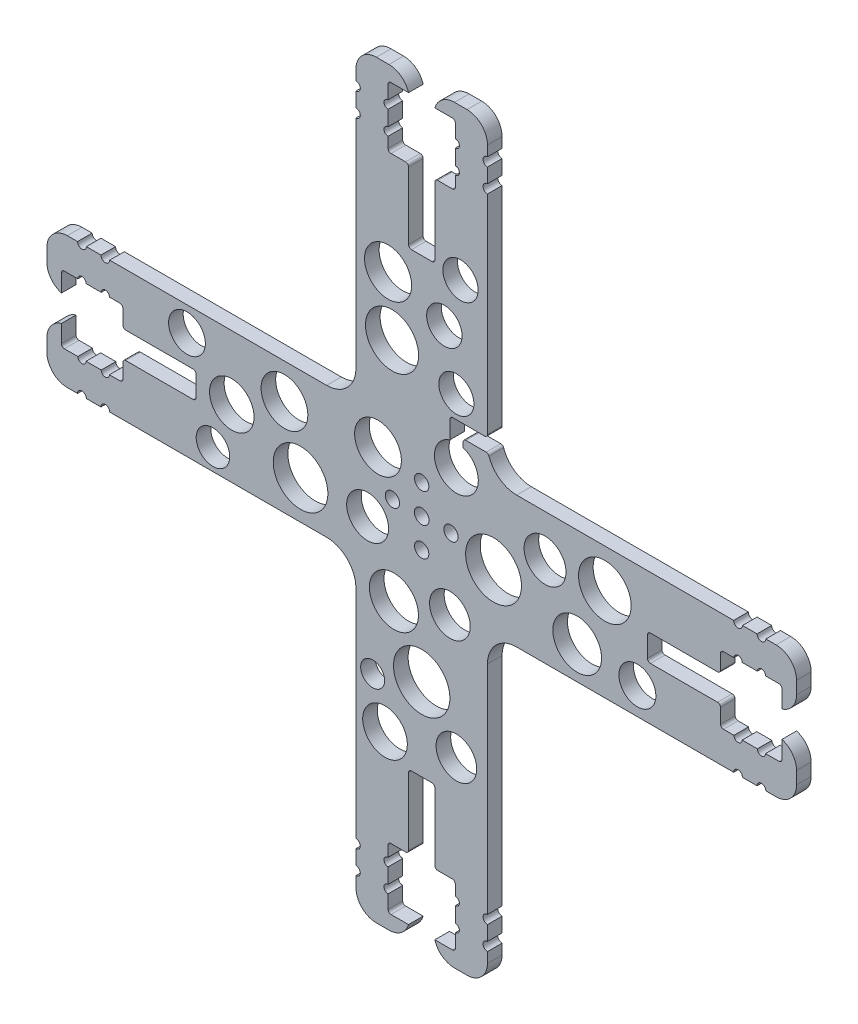
SolidWorks part; units mm, degrees
ref_plane "Front Plane" through (0, 0, 0) normal (0, 0, 1) x (1, 0, 0)
ref_plane "Top Plane" through (0, 0, 0) normal (0, 1, 0) x (1, 0, 0)
ref_plane "Right Plane" through (0, 0, 0) normal (1, 0, 0) x (0, 0, -1)
sketch "Esquisse1" plane through (0, 0, 0) normal (0, 0, 1) x (1, 0, 0)
  line L0 (0, 159.2308) -> (0, -15.7846) construction
  line L1 (-22.5, 22.5) -> (-22.5, 128.2082)
  line L2 (-22.5, 128.2082) -> (-4.5, 128.2082)
  line L3 (-4.5, 128.2082) -> (-4.5, 123.2082)
  line L4 (-4.5, 123.2082) -> (-11.5, 123.2082)
  line L5 (-11.5, 123.2082) -> (-11.5, 102.2082)
  line L6 (-11.5, 102.2082) -> (-4.5, 102.2082)
  line L7 (-4.5, 102.2082) -> (-4.5, 77.2082)
  line L8 (-4.5, 77.2082) -> (4.5, 77.2082)
  line L9 (4.5, 77.2082) -> (4.5, 102.2082)
  line L10 (4.5, 102.2082) -> (11.5, 102.2082)
  line L11 (11.5, 102.2082) -> (11.5, 123.2082)
  line L12 (11.5, 123.2082) -> (4.5, 123.2082)
  line L13 (4.5, 123.2082) -> (4.5, 128.2082)
  line L14 (4.5, 128.2082) -> (22.5, 128.2082)
  line L15 (22.5, 128.2082) -> (22.5, 22.5)
  line L16 (22.5, 22.5) -> (128.2082, 22.5)
  line L17 (128.2082, 22.5) -> (128.2082, 4.5)
  line L18 (128.2082, 4.5) -> (123.2082, 4.5)
  line L19 (123.2082, 4.5) -> (123.2082, 11.5)
  line L20 (123.2082, 11.5) -> (102.2082, 11.5)
  line L21 (102.2082, 11.5) -> (102.2082, 4.5)
  line L22 (102.2082, 4.5) -> (77.2082, 4.5)
  line L23 (77.2082, 4.5) -> (77.2082, -4.5)
  line L24 (77.2082, -4.5) -> (102.2082, -4.5)
  line L25 (102.2082, -4.5) -> (102.2082, -11.5)
  line L26 (102.2082, -11.5) -> (123.2082, -11.5)
  line L27 (123.2082, -11.5) -> (123.2082, -4.5)
  line L28 (123.2082, -4.5) -> (128.2082, -4.5)
  line L29 (128.2082, -4.5) -> (128.2082, -22.5)
  line L30 (128.2082, -22.5) -> (22.5, -22.5)
  line L31 (22.5, -22.5) -> (22.5, -128.2082)
  line L32 (22.5, -128.2082) -> (4.5, -128.2082)
  line L33 (4.5, -128.2082) -> (4.5, -123.2082)
  line L34 (4.5, -123.2082) -> (11.5, -123.2082)
  line L35 (11.5, -123.2082) -> (11.5, -102.2082)
  line L36 (11.5, -102.2082) -> (4.5, -102.2082)
  line L37 (4.5, -102.2082) -> (4.5, -77.2082)
  line L38 (4.5, -77.2082) -> (-4.5, -77.2082)
  line L39 (-4.5, -77.2082) -> (-4.5, -102.2082)
  line L40 (-4.5, -102.2082) -> (-11.5, -102.2082)
  line L41 (-11.5, -102.2082) -> (-11.5, -123.2082)
  line L42 (-11.5, -123.2082) -> (-4.5, -123.2082)
  line L43 (-4.5, -123.2082) -> (-4.5, -128.2082)
  line L44 (-4.5, -128.2082) -> (-22.5, -128.2082)
  line L45 (-22.5, -128.2082) -> (-22.5, -22.5)
  line L46 (-22.5, -22.5) -> (-128.2082, -22.5)
  line L47 (-128.2082, -22.5) -> (-128.2082, -4.5)
  line L48 (-128.2082, -4.5) -> (-123.2082, -4.5)
  line L49 (-123.2082, -4.5) -> (-123.2082, -11.5)
  line L50 (-123.2082, -11.5) -> (-102.2082, -11.5)
  line L51 (-102.2082, -11.5) -> (-102.2082, -4.5)
  line L52 (-102.2082, -4.5) -> (-77.2082, -4.5)
  line L53 (-77.2082, -4.5) -> (-77.2082, 4.5)
  line L54 (-77.2082, 4.5) -> (-102.2082, 4.5)
  line L55 (-102.2082, 4.5) -> (-102.2082, 11.5)
  line L56 (-102.2082, 11.5) -> (-123.2082, 11.5)
  line L57 (-123.2082, 11.5) -> (-123.2082, 4.5)
  line L58 (-123.2082, 4.5) -> (-128.2082, 4.5)
  line L59 (-128.2082, 4.5) -> (-128.2082, 22.5)
  line L60 (-128.2082, 22.5) -> (-22.5, 22.5)
  line L61 (-24.5698, 123.2082) -> (43.5937, 123.2082) construction
  line L62 (123.2082, 24.5698) -> (123.2082, -43.5937) construction
  line L63 (24.5698, -123.2082) -> (-43.5937, -123.2082) construction
  line L64 (-123.2082, -24.5698) -> (-123.2082, 43.5937) construction
  line L65 (-148.0023, 0) -> (163.5643, 0) construction
  circle A0 centre (0, 0) radius 2.5
  circle A1 centre (-80.2824, 14.1103) radius 6.2904
  circle A2 centre (-64.9494, 0.6296) radius 7.6187
  circle A3 centre (-41.4305, -9.3429) radius 9.3429
  circle A4 centre (-46.9444, 10.5137) radius 8
  circle A5 centre (-71.3951, -15.2254) radius 5.734
  circle A6 centre (42.1879, 8.0594) radius 7.1686
  circle A7 centre (24.5698, -3.6089) radius 9.551
  circle A8 centre (11.8627, 20.2507) radius 7.5
  circle A9 centre (-14.9441, 12.9829) radius 8
  circle A10 centre (-10.1433, 47.064) radius 9.0827
  circle A11 centre (11.8627, 42.1489) radius 6
  circle A12 centre (-18.5, -9.3429) radius 7.1678
  circle A13 centre (0, -49.0636) radius 9.6471
  circle A14 centre (-16.7647, -55.0598) radius 4.1145
  circle A15 centre (11.8627, -65.5127) radius 6.9485
  circle A16 centre (-12.5425, -70.0598) radius 7.6364
  circle A17 centre (9.6471, -24.3763) radius 6.9631
  circle A18 centre (-9.5049, -29.9285) radius 8.3862
  circle A19 centre (53.1834, -11.3064) radius 8.3279
  circle A20 centre (62.6447, 9.2453) radius 9
  circle A21 centre (13.2718, 76.5762) radius 6.033
  circle A22 centre (-11.5, 66.6049) radius 8.0615
  circle A23 centre (7.7598, 60.3029) radius 6.0616
  circle A24 centre (73.7695, -13.2445) radius 6.3276
  circle A25 centre (10, 0) radius 2.4404
  circle A26 centre (0, -10) radius 2.4404
  circle A27 centre (-10, 0) radius 2.4404
  circle A28 centre (0, 10) radius 2.4404
  point P19 (0, 77.2082)
  point P23 (0, 123.2082)
  point P74 (0, 0)
  point P76 (123.2082, 0)
  point P81 (0, -123.2082)
  point P84 (-123.2082, 0)
  point P129 (0, 120.2082)
  point P132 (120.2082, 0)
  point P133 (0, -120.2082)
  point P136 (-120.2082, 0)
  point P144 (0, 0)
  dimension "D6" = 4
  dimension "D9" = 170
  dimension "D10" = 10
  dimension "D1" = 9
  dimension "D2" = 23
  dimension "D3" = 21
  dimension "D4" = 45
  dimension "D5" = 25
  dimension "D7" = 3
  dimension "D8" = 5
  dimension "D11" = 4
extrude "Boss.-Extru.1" add sketch "Esquisse1" along normal blind 5
fillet "Congé1" radius 7 16 edges at (128.2082, 4.5, 2.5) (128.2082, -4.5, 2.5) (4.5, -128.2082, 2.5) (-4.5, -128.2082, 2.5) (-128.2082, -4.5, 2.5) (-128.2082, 4.5, 2.5) (-4.5, 128.2082, 2.5) (4.5, 128.2082, 2.5) (22.5, 128.2082, 2.5) (-22.5, 128.2082, 2.5) (-128.2082, 22.5, 2.5) (-128.2082, -22.5, 2.5) (-22.5, -128.2082, 2.5) (22.5, -128.2082, 2.5) (128.2082, -22.5, 2.5) (128.2082, 22.5, 2.5)
fillet "Congé2" radius 10 4 edges at (-22.5, 22.5, 2.5) (22.5, 22.5, 2.5) (22.5, -22.5, 2.5) (-22.5, -22.5, 2.5)
fillet "Congé3" radius 1 32 edges at (123.2082, -11.5, 2.5) (102.2082, -11.5, 2.5) (77.2082, -4.5, 2.5) (123.2082, 11.5, 2.5) (102.2082, -4.5, 2.5) (102.2082, 11.5, 2.5) (77.2082, 4.5, 2.5) (102.2082, 4.5, 2.5) (11.5, 123.2082, 2.5) (11.5, 102.2082, 2.5) (4.5, 77.2082, 2.5) (4.5, 102.2082, 2.5) (-4.5, 77.2082, 2.5) (-4.5, 102.2082, 2.5) (-11.5, 102.2082, 2.5) (-11.5, 123.2082, 2.5) (-123.2082, 11.5, 2.5) (-102.2082, 11.5, 2.5) (-102.2082, 4.5, 2.5) (-77.2082, 4.5, 2.5) (-77.2082, -4.5, 2.5) (-102.2082, -4.5, 2.5) (-102.2082, -11.5, 2.5) (-123.2082, -11.5, 2.5) (-4.5, -77.2082, 2.5) (4.5, -77.2082, 2.5) (4.5, -102.2082, 2.5) (-4.5, -102.2082, 2.5) (11.5, -123.2082, 2.5) (11.5, -102.2082, 2.5) (-11.5, -123.2082, 2.5) (-11.5, -102.2082, 2.5)
sketch "Esquisse2" plane through (0, 0, 0) normal (0, 0, -1) x (-1, 0, 0)
  line L0 (-121.2082, 22.5) -> (-32.5, 22.5) construction
  line L1 (-123.2082, 10.5) -> (-123.2082, 4.5) construction
  line L2 (-83.3281, 0) -> (-132.2147, 0) construction
  line L3 (-117.7082, 22.5) -> (-114.7082, 22.5)
  line L4 (-109.7082, 22.5) -> (-106.7082, 22.5)
  line L5 (-117.7082, -22.5) -> (-114.7082, -22.5)
  line L6 (-109.7082, -22.5) -> (-106.7082, -22.5)
  line L7 (22.5, 117.7082) -> (22.5, 114.7082)
  line L8 (22.5, 109.7082) -> (22.5, 106.7082)
  line L9 (-22.5, 117.7082) -> (-22.5, 114.7082)
  line L10 (-22.5, 109.7082) -> (-22.5, 106.7082)
  line L11 (117.7082, -22.5) -> (114.7082, -22.5)
  line L12 (109.7082, -22.5) -> (106.7082, -22.5)
  line L13 (117.7082, 22.5) -> (114.7082, 22.5)
  line L14 (109.7082, 22.5) -> (106.7082, 22.5)
  line L15 (-22.5, -117.7082) -> (-22.5, -114.7082)
  line L16 (-22.5, -109.7082) -> (-22.5, -106.7082)
  line L17 (22.5, -117.7082) -> (22.5, -114.7082)
  line L18 (22.5, -109.7082) -> (22.5, -106.7082)
  line L19 (-103.2082, 11.5) -> (-122.2082, 11.5) construction
  line L20 (-116.2082, 24.0368) -> (-116.2082, 6.6966) construction
  line L21 (-108.2082, 24.0368) -> (-108.2082, 7.2406) construction
  line L22 (-114.8082, 11.5) -> (-117.6082, 11.5)
  line L23 (-109.6082, 11.5) -> (-106.8082, 11.5)
  line L24 (-109.6082, -11.5) -> (-106.8082, -11.5)
  line L25 (-114.8082, -11.5) -> (-117.6082, -11.5)
  line L26 (-11.5, 114.8082) -> (-11.5, 117.6082)
  line L27 (-11.5, 109.6082) -> (-11.5, 106.8082)
  line L28 (11.5, 114.8082) -> (11.5, 117.6082)
  line L29 (11.5, 109.6082) -> (11.5, 106.8082)
  line L30 (114.8082, 11.5) -> (117.6082, 11.5)
  line L31 (109.6082, 11.5) -> (106.8082, 11.5)
  line L32 (114.8082, -11.5) -> (117.6082, -11.5)
  line L33 (109.6082, -11.5) -> (106.8082, -11.5)
  line L34 (11.5, -114.8082) -> (11.5, -117.6082)
  line L35 (11.5, -109.6082) -> (11.5, -106.8082)
  line L36 (-11.5, -114.8082) -> (-11.5, -117.6082)
  line L37 (-11.5, -109.6082) -> (-11.5, -106.8082)
  arc A0 (-117.7082, 22.5) -> (-114.7082, 22.5) centre (-116.2082, 22.5) ccw
  arc A1 (-109.7082, 22.5) -> (-106.7082, 22.5) centre (-108.2082, 22.5) ccw
  arc A2 (-109.7082, -22.5) -> (-106.7082, -22.5) centre (-108.2082, -22.5) cw
  arc A3 (-117.7082, -22.5) -> (-114.7082, -22.5) centre (-116.2082, -22.5) cw
  arc A4 (22.5, 117.7082) -> (22.5, 114.7082) centre (22.5, 116.2082) ccw
  arc A5 (22.5, 109.7082) -> (22.5, 106.7082) centre (22.5, 108.2082) ccw
  arc A6 (-22.5, 117.7082) -> (-22.5, 114.7082) centre (-22.5, 116.2082) cw
  arc A7 (-22.5, 109.7082) -> (-22.5, 106.7082) centre (-22.5, 108.2082) cw
  arc A8 (117.7082, -22.5) -> (114.7082, -22.5) centre (116.2082, -22.5) ccw
  arc A9 (109.7082, -22.5) -> (106.7082, -22.5) centre (108.2082, -22.5) ccw
  arc A10 (117.7082, 22.5) -> (114.7082, 22.5) centre (116.2082, 22.5) cw
  arc A11 (109.7082, 22.5) -> (106.7082, 22.5) centre (108.2082, 22.5) cw
  arc A12 (-22.5, -117.7082) -> (-22.5, -114.7082) centre (-22.5, -116.2082) ccw
  arc A13 (-22.5, -109.7082) -> (-22.5, -106.7082) centre (-22.5, -108.2082) ccw
  arc A14 (22.5, -117.7082) -> (22.5, -114.7082) centre (22.5, -116.2082) cw
  arc A15 (22.5, -109.7082) -> (22.5, -106.7082) centre (22.5, -108.2082) cw
  arc A16 (-114.8082, 11.5) -> (-117.6082, 11.5) centre (-116.2082, 11.5) ccw
  arc A17 (-109.6082, 11.5) -> (-106.8082, 11.5) centre (-108.2082, 11.5) cw
  arc A18 (-109.6082, -11.5) -> (-106.8082, -11.5) centre (-108.2082, -11.5) ccw
  arc A19 (-114.8082, -11.5) -> (-117.6082, -11.5) centre (-116.2082, -11.5) cw
  arc A20 (-11.5, 114.8082) -> (-11.5, 117.6082) centre (-11.5, 116.2082) cw
  arc A21 (-11.5, 109.6082) -> (-11.5, 106.8082) centre (-11.5, 108.2082) ccw
  arc A22 (11.5, 114.8082) -> (11.5, 117.6082) centre (11.5, 116.2082) ccw
  arc A23 (11.5, 109.6082) -> (11.5, 106.8082) centre (11.5, 108.2082) cw
  arc A24 (114.8082, 11.5) -> (117.6082, 11.5) centre (116.2082, 11.5) cw
  arc A25 (109.6082, 11.5) -> (106.8082, 11.5) centre (108.2082, 11.5) ccw
  arc A26 (114.8082, -11.5) -> (117.6082, -11.5) centre (116.2082, -11.5) ccw
  arc A27 (109.6082, -11.5) -> (106.8082, -11.5) centre (108.2082, -11.5) cw
  arc A28 (11.5, -114.8082) -> (11.5, -117.6082) centre (11.5, -116.2082) cw
  arc A29 (11.5, -109.6082) -> (11.5, -106.8082) centre (11.5, -108.2082) ccw
  arc A30 (-11.5, -114.8082) -> (-11.5, -117.6082) centre (-11.5, -116.2082) ccw
  arc A31 (-11.5, -109.6082) -> (-11.5, -106.8082) centre (-11.5, -108.2082) cw
  point P58 (0, 0)
  dimension "D1" = 5.5
  dimension "D2" = 5
  dimension "D3" = 3
  dimension "D4" = 3
  dimension "D5" = 4
extrude "Enlèv. mat.-Extru.1" cut sketch "Esquisse2" against normal blind 5
sketch "Esquisse3" plane through (0, 0, 0) normal (0, 0, -1) x (-1, 0, 0)
  line L0 (-23.0619, 34.5102) -> (-9.6127, 34.5102)
  line L2 (-9.6127, 34.5102) -> (-9.6127, 27.4052)
  line L3 (-9.6127, 27.4052) -> (-14.1127, 27.4052)
  line L4 (-14.1127, 27.4052) -> (-14.1127, 30.0102)
  line L5 (-14.1127, 30.0102) -> (-23.0619, 30.0102)
  line L6 (-23.0619, 30.0102) -> (-23.0619, 34.5102)
  circle A0 centre (-11.8627, 20.2507) radius 7.5 construction
  dimension "D1" = 4.5
  dimension "D2" = 4.5
extrude "Enlèv. mat.-Extru.2" cut sketch "Esquisse3" against normal blind 10
fillet "Congé4" radius 1 4 edges at (22.5, 34.5102, 2.5) (22.8149, 30.0102, 2.5) (9.6127, 34.5102, 2.5) (14.1127, 30.0102, 2.5)
